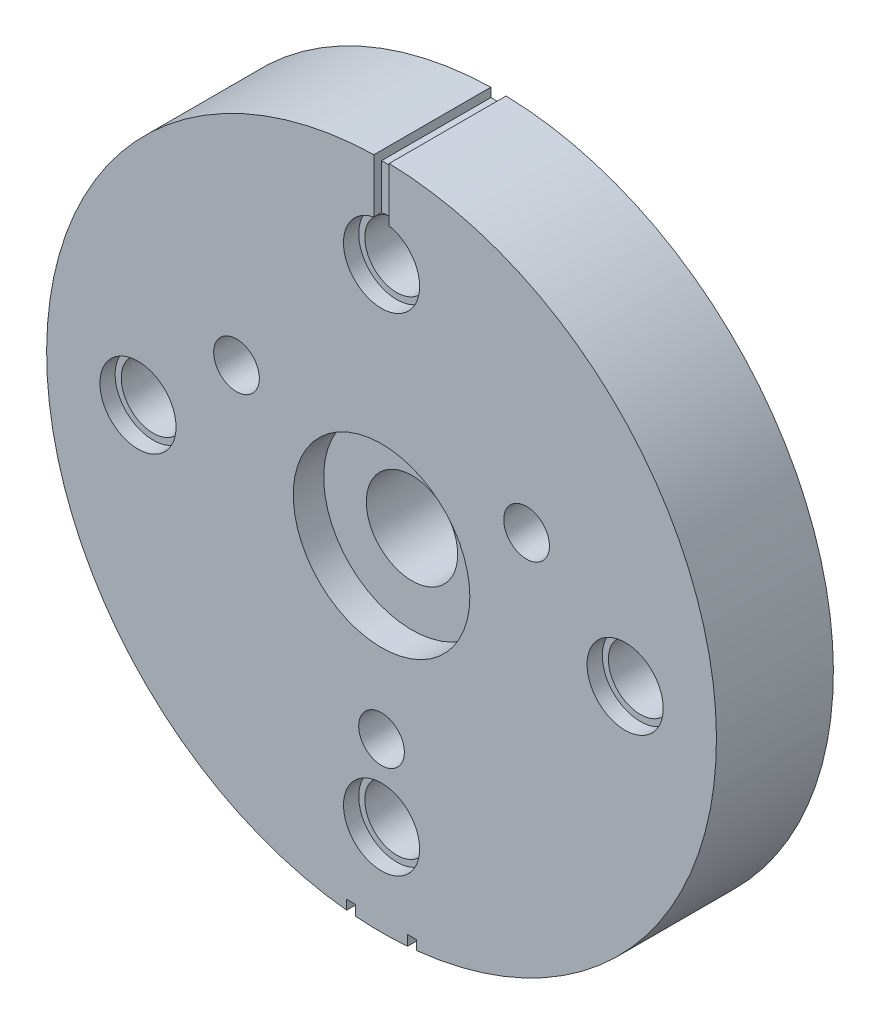
SolidWorks part; units mm, degrees
ref_plane "Front Plane" through (0, 0, 0) normal (0, 0, 1) x (1, 0, 0)
ref_plane "Top Plane" through (0, 0, 0) normal (0, 1, 0) x (1, 0, 0)
ref_plane "Right Plane" through (0, 0, 0) normal (1, 0, 0) x (0, 0, -1)
sketch "Sketch5" plane through (0, 0, 0) normal (0, 0, 1) x (1, 0, 0)
  circle A0 centre (0, 0) radius 11
sketch "Sketch6" plane through (0, 0, 0) normal (0, 0, 1) x (1, 0, 0)
  circle A0 centre (0, 0) radius 2.9
  circle A1 centre (0, 0) radius 1.5
sketch "Sketch7" plane through (0, 0, 0) normal (0, 0, 1) x (1, 0, 0)
  circle A6 centre (-4.7631, 2.75) radius 0.75
  circle A7 centre (4.7631, 2.75) radius 0.75
  circle A8 centre (0, -5.5) radius 0.75
sketch "Sketch8" plane through (0, 0, 0) normal (0, 0, 1) x (1, 0, 0)
  line L0 (0, 11) -> (0, -11) construction
  line L1 (11, 0) -> (-11, 0) construction
  circle A0 centre (0, 0) radius 11 construction
  circle A1 centre (-8, 0) radius 1.05
  circle A2 centre (0, -8) radius 1.05
  circle A3 centre (8, 0) radius 1.05
  circle A4 centre (0, 8) radius 1.05
  circle A5 centre (-8, 0) radius 1.25
  circle A6 centre (0, -8) radius 1.25
  circle A7 centre (8, 0) radius 1.25
  circle A8 centre (0, 8) radius 1.25
extrude "Boss-Extrude3" add sketch "Sketch5" against normal blind 3.84
extrude "Cut-Extrude16" cut sketch "Sketch6" against normal blind 3.84 contours A1
extrude "Cut-Extrude17" cut sketch "Sketch6<8>" against normal blind 1
sketch "Sketch6<8>" plane through (0, 0, 0) normal (0, 0, 1) x (1, 0, 0) same geometry as "Sketch6"
extrude "Cut-Extrude18" cut sketch "Sketch7" against normal blind 2
extrude "Cut-Extrude20" cut sketch "Sketch8" against normal blind 3 contours A2 | A3 | A4 | A1
extrude "Cut-Extrude21" cut sketch "Sketch8<4>" against normal blind 0.5
sketch "Sketch8<4>" plane through (0, 0, 0) normal (0, 0, 1) x (1, 0, 0) same geometry as "Sketch8"
sketch "Sketch15" plane through (0, 0, 0) normal (0, 0, 1) x (1, 0, 0)
  line L5 (-1.1469, -11) -> (-1.1469, -10.6297) construction
  line L6 (-1.1469, -10.6297) -> (-0.8473, -10.6297) construction
  line L7 (-0.8473, -10.6297) -> (-0.8473, -11) construction
  line L10 (1.1541, -11) -> (1.1541, -10.6297) construction
  line L11 (1.1541, -10.6297) -> (0.8535, -10.6297) construction
  line L12 (0.8535, -10.6297) -> (0.8535, -11) construction
  line L14 (-1.1469, -10.6297) -> (-0.8473, -10.6297)
  line L15 (-1.1469, -10.6297) -> (-1.1469, -11)
  line L16 (-1.1469, -11) -> (-0.8473, -11)
  line L17 (-0.8473, -10.6297) -> (-0.8473, -11)
  line L18 (0.8535, -10.6297) -> (1.1541, -10.6297)
  line L19 (0.8535, -10.6297) -> (0.8535, -11)
  line L20 (0.8535, -11) -> (1.1541, -11)
  line L21 (1.1541, -10.6297) -> (1.1541, -11)
extrude "Cut-Extrude22" cut sketch "Sketch15" against normal blind 3.84
sketch "Sketch16" plane through (0, 0, 0) normal (0, 0, 1) x (1, 0, 0)
  line L11 (0, 10.7016) -> (0.25, 10.7016) construction
  line L13 (-0.25, 11) -> (0.25, 11)
  line L14 (-0.25, 11) -> (-0.25, 10.7016)
  line L15 (-0.25, 10.7016) -> (0.25, 10.7016)
  line L16 (0.25, 11) -> (0.25, 10.7016)
extrude "Cut-Extrude23" cut sketch "Sketch16" against normal blind 3.84
sketch "Sketch17" plane through (0, 0, 0) normal (0, 0, 1) x (1, 0, 0)
  line L3 (-0.25, 10.7016) -> (0.25, 10.7016)
  line L4 (-0.25, 10.7016) -> (-0.25, 9.1015)
  line L5 (-0.25, 9.1015) -> (0.25, 9.1015)
  line L6 (0.25, 10.7016) -> (0.25, 9.1015)
extrude "Cut-Extrude24" cut sketch "Sketch17" against normal blind 0.25
